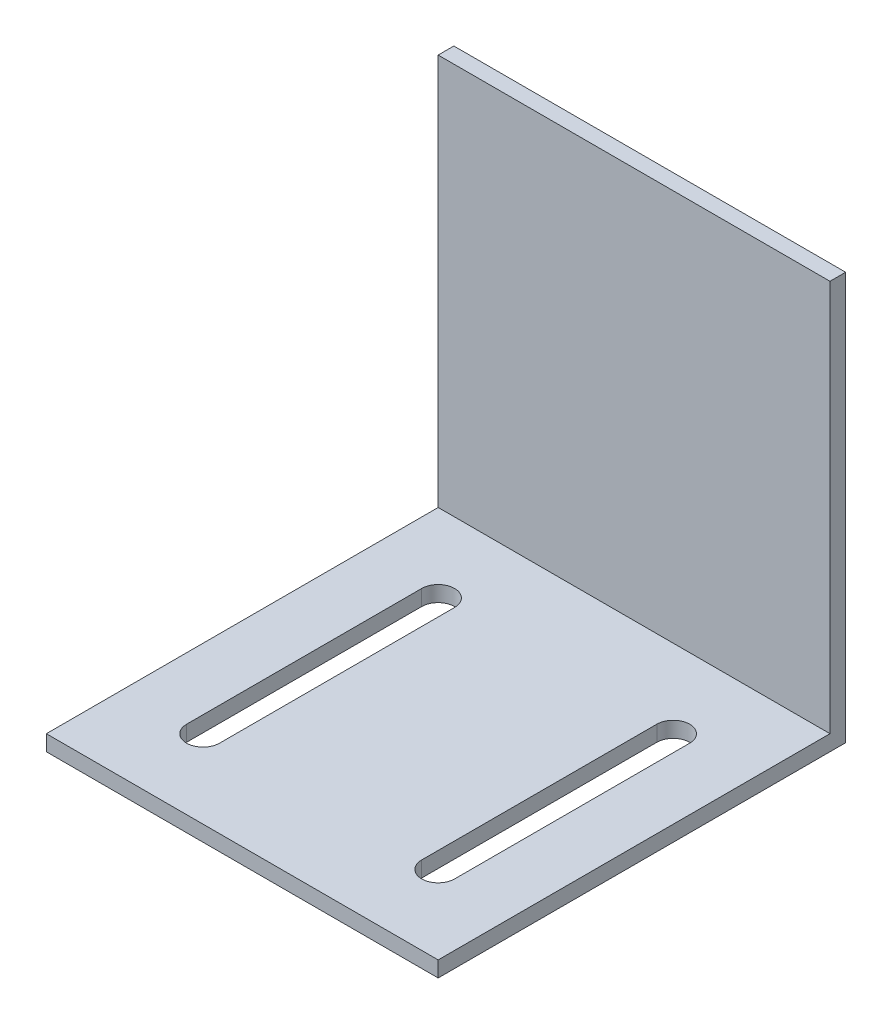
SolidWorks part; units mm, degrees
ref_plane "Front Plane" through (0, 0, 0) normal (0, 0, 1) x (1, 0, 0)
ref_plane "Top Plane" through (0, 0, 0) normal (0, 1, 0) x (1, 0, 0)
ref_plane "Right Plane" through (0, 0, 0) normal (1, 0, 0) x (0, 0, -1)
sketch "Sketch1" plane through (0, 0, 0) normal (0, 1, 0) x (1, 0, 0)
  line L0 (15, 0) -> (-15, 0) construction
  line L1 (-25, -25) -> (25, -25)
  line L2 (-25, -25) -> (-25, 25)
  line L3 (-25, 25) -> (25, 25)
  line L4 (25, -25) -> (25, 25)
  line L5 (-25, -25) -> (25, 25) construction
  line L6 (-25, 25) -> (25, -25) construction
  line L7 (-15, -15) -> (-15, 15) construction
  line L8 (-17.1, 15) -> (-17.1, -15)
  line L9 (-12.9, 15) -> (-12.9, -15)
  line L10 (0, 0) -> (0, 9.909) construction
  line L11 (17.1, 15) -> (17.1, -15)
  line L12 (12.9, 15) -> (12.9, -15)
  arc A0 (-12.9, 15) -> (-17.1, 15) centre (-15, 15) ccw
  arc A1 (-17.1, -15) -> (-12.9, -15) centre (-15, -15) ccw
  arc A2 (12.9, 15) -> (17.1, 15) centre (15, 15) cw
  arc A3 (17.1, -15) -> (12.9, -15) centre (15, -15) cw
  point P0 (0, 0)
  point P9 (0, 0)
  point P12 (-15, 0)
  dimension "D5" = 4.2
  dimension "D6" = 4.2
  dimension "D1" = 50
  dimension "D2" = 50
  dimension "D3" = 30
  dimension "D4" = 30
extrude "Boss-Extrude1" add sketch "Sketch1" along normal blind 2
sketch "Sketch2" plane through (0, 0, 0) normal (0, -1, 0) x (1, 0, 0)
  line L1 (25, -25) -> (-25, -25)
  line L2 (25, -25) -> (25, -27)
  line L3 (25, -27) -> (-25, -27)
  line L4 (-25, -25) -> (-25, -27)
  dimension "D1" = 2
extrude "Boss-Extrude2" add sketch "Sketch2" against normal blind 52
sketch "Sketch3" plane through (0, 0, -25) normal (0, 0, 1) x (1, 0, 0)
  line L0 (-25, 52) -> (25, 2) construction
  line L2 (15.6, 11.4) -> (-15.6, 11.4) construction
  line L3 (15.6, 11.4) -> (15.6, 42.6) construction
  line L4 (15.6, 42.6) -> (-15.6, 42.6) construction
  line L5 (-15.6, 11.4) -> (-15.6, 42.6) construction
  line L6 (15.6, 11.4) -> (-15.6, 42.6) construction
  line L7 (15.6, 42.6) -> (-15.6, 11.4) construction
  circle A0 centre (-15.6, 42.6) radius 1.0518
  point P4 (0, 27)
  dimension "D1" = 31.2
  dimension "D2" = 31.2
